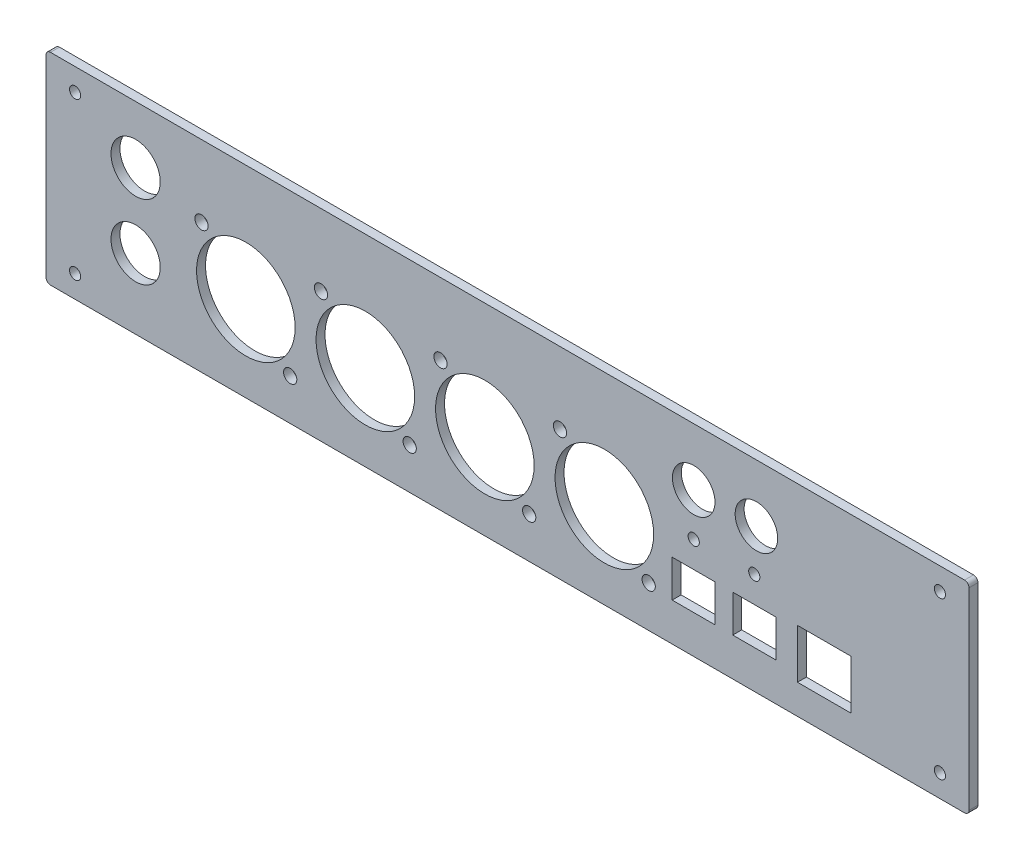
SolidWorks part; units mm, degrees
ref_plane "Front" through (0, 0, 0) normal (0, 0, 1) x (1, 0, 0)
ref_plane "Top" through (0, 0, 0) normal (0, 1, 0) x (1, 0, 0)
ref_plane "Right" through (0, 0, 0) normal (1, 0, 0) x (0, 0, -1)
sketch "草图5" plane through (0, 0, 0) normal (0, 0, 1) x (1, 0, 0)
  line L1 (-106.8845, -4.911) -> (99.1155, -4.911)
  line L2 (-106.8845, -4.911) -> (-106.8845, 40.089)
  line L3 (-106.8845, 40.089) -> (99.1155, 40.089)
  line L4 (99.1155, -4.911) -> (99.1155, 40.089)
  line L7 (-44.3845, -4.911) -> (40.6155, -4.911)
  line L9 (-44.3845, 40.089) -> (40.6155, 40.089)
  dimension "D1" = 206
  dimension "D2" = 45
  dimension "D3" = 85
extrude "凸台-拉伸3" add sketch "草图5" along normal blind 2 contours L4 L3 L2 L1
sketch "草图6" plane through (0, 0, 2) normal (0, 0, 1) x (1, 0, 0)
  line L0 (99.1155, -2.911) -> (-106.8845, -2.911) construction
  line L1 (99.1155, -4.911) -> (99.1155, 40.089) construction
  line L2 (-106.8845, -4.911) -> (-106.8845, 40.089) construction
  line L3 (-106.8845, -4.911) -> (99.1155, -4.911) construction
  line L4 (-106.8845, 0.089) -> (99.1155, 0.089) construction
  line L5 (99.1155, 1.689) -> (-106.8845, 1.689) construction
  line L6 (-1.8845, -2.911) -> (-1.8845, 40.089) construction
  line L7 (-81.8845, 14.189) -> (13.7097, 14.189) construction
  line L8 (-81.8845, 1.689) -> (109.1155, 1.689)
  line L9 (-81.8845, 1.689) -> (-81.8845, 0.089)
  line L10 (-81.8845, 0.089) -> (109.1155, 0.089)
  line L11 (109.1155, 1.689) -> (109.1155, 0.089)
  line L12 (61.4188, 10.089) -> (97.4452, 10.089)
  line L13 (-86.8845, 10.7454) -> (-86.8845, 27.2669) construction
  line L14 (-68.7606, 20.6651) -> (-44.2612, -3.8343) construction
  line L15 (-50.4178, 28.9923) -> (-20.8112, -0.6143) construction
  line L16 (-22.3851, 27.6296) -> (4.496, 0.7485) construction
  line L17 (17.7255, 14.189) -> (29.6473, 2.2672) construction
  line L18 (32.8655, 3.589) -> (42.4655, 3.589)
  line L19 (32.8655, 3.589) -> (32.8655, 11.889)
  line L20 (32.8655, 11.889) -> (42.4655, 11.889)
  line L21 (42.4655, 3.589) -> (42.4655, 11.889)
  line L22 (32.8655, 3.589) -> (42.4655, 11.889) construction
  line L23 (32.8655, 11.889) -> (42.4655, 3.589) construction
  line L24 (46.3855, 3.589) -> (55.9855, 3.589)
  line L25 (46.3855, 3.589) -> (46.3855, 11.889)
  line L26 (46.3855, 11.889) -> (55.9855, 11.889)
  line L27 (55.9855, 3.589) -> (55.9855, 11.889)
  line L28 (46.3855, 3.589) -> (55.9855, 11.889) construction
  line L29 (46.3855, 11.889) -> (55.9855, 3.589) construction
  line L30 (60.8255, 1.689) -> (72.8255, 1.689)
  line L31 (60.8255, 1.689) -> (60.8255, 12.689)
  line L32 (60.8255, 12.689) -> (72.8255, 12.689)
  line L33 (72.8255, 1.689) -> (72.8255, 12.689)
  line L34 (60.8255, 1.689) -> (72.8255, 12.689) construction
  line L35 (60.8255, 12.689) -> (72.8255, 1.689) construction
  circle A0 centre (-62.2845, 14.189) radius 11
  circle A1 centre (-35.6145, 14.189) radius 11
  circle A2 centre (-8.9445, 14.189) radius 11
  circle A3 centre (17.7255, 14.189) radius 11
  circle A4 centre (-72.1845, 24.089) radius 1.4749
  circle A5 centre (-52.3845, 4.289) radius 1.4749
  circle A6 centre (-45.5145, 24.089) radius 1.4749
  circle A7 centre (-25.7145, 4.289) radius 1.4749
  circle A8 centre (-18.8445, 24.089) radius 1.4749
  circle A9 centre (0.9555, 4.289) radius 1.4749
  circle A10 centre (7.8255, 24.089) radius 1.4749
  circle A11 centre (27.6255, 4.289) radius 1.4749
  circle A12 centre (37.6655, 17.739) radius 1.25
  circle A13 centre (51.1855, 17.739) radius 1.25
  circle A14 centre (51.6655, 27.2669) radius 4.75
  circle A15 centre (37.6655, 27.2669) radius 4.75
  circle A16 centre (-86.8845, 27.2669) radius 5.5
  circle A17 centre (-86.8845, 10.7454) radius 5.5
  circle A18 centre (-86.8845, 10.7454) radius 8 construction
  circle A19 centre (-86.8845, 27.2669) radius 8 construction
  text T0 "铜柱支撑高度" font "Century Gothic" height in points 9
  text T1 "pcb基板高度" font "Century Gothic" height in points 7
  point P31 (-81.8845, 0.889)
  point P35 (51.1855, 7.739)
  point P36 (37.6655, 7.739)
  point P37 (-35.6145, 14.189)
  point P42 (-62.2845, 14.189)
  point P43 (-8.9445, 14.189)
  point P73 (66.8255, 7.189)
  dimension "D6" = 22
  dimension "D7" = 22
  dimension "D8" = 22
  dimension "D9" = 22
  dimension "D33" = 2.5
  dimension "D34" = 2.5
  dimension "D40" = 9.5
  dimension "D41" = 9.5
  dimension "D43" = 11
  dimension "D44" = 11
  dimension "D46" = 16
  dimension "D48" = 16
  dimension "D1" = 2
  dimension "D2" = 3
  dimension "D3" = 1.6
  dimension "D4" = 191
  dimension "D5" = 12.5
  dimension "D10" = 9.9
  dimension "D11" = 9.9
  dimension "D12" = 45
  dimension "D13" = 45
  dimension "D14" = 45
  dimension "D15" = 45
  dimension "D16" = 9.9
  dimension "D17" = 9.9
  dimension "D18" = 9.9
  dimension "D19" = 9.9
  dimension "D20" = 9.9
  dimension "D21" = 9.9
  dimension "D22" = 19.6
  dimension "D23" = 26.67
  dimension "D24" = 26.67
  dimension "D25" = 26.67
  dimension "D26" = 9.6
  dimension "D27" = 9.6
  dimension "D28" = 8.3
  dimension "D29" = 8.3
  dimension "D30" = 13.52
  dimension "D31" = 1.9
  dimension "D32" = 5.24
  dimension "D35" = 10
  dimension "D36" = 10
  dimension "D37" = 4.84
  dimension "D38" = 11
  dimension "D39" = 12
  dimension "D42" = 25
  dimension "D45" = 14
  dimension "D47" = 8.4
  dimension "D49" = 5
extrude "切除-拉伸1" cut sketch "草图6" against normal blind 10 contours A1 | A2 | A3 | L18 L21 L20 L19 | L8 L33 L32 L31 | A13 | A12 | A11 | A10 | A8 | A7 | A9 | A6 | A5 | A4 | A15 | A0 | L27 L26 L25 L24 | A14 | A16 | A17 region at (66.8255, 7.189, 2) region at (37.6655, 7.739, 2) region at (-35.6145, 14.189, 2) region at (-8.9445, 14.189, 2) region at (17.7255, 14.189, 2) region at (-72.1845, 24.089, 2) region at (-52.3845, 4.289, 2) region at (-45.5145, 24.089, 2) region at (-25.7145, 4.289, 2) region at (-18.8445, 24.089, 2) region at (0.9555, 4.289, 2) region at (7.8255, 24.089, 2) region at (27.6255, 4.289, 2) region at (37.6655, 17.739, 2) region at (51.1855, 17.739, 2) region at (37.6655, 27.2669, 2)
sketch "草图1" plane through (0, 0, 0) normal (0, 0, 1) x (1, 0, 0)
  line L0 (92.6155, 0.089) -> (-100.3845, 0.089)
  line L1 (92.6155, 0.089) -> (92.6155, 35.089)
  line L2 (92.6155, 35.089) -> (-100.3845, 35.089)
  line L3 (-100.3845, 0.089) -> (-100.3845, 35.089)
  line L4 (92.6155, 0.089) -> (-100.3845, 35.089) construction
  line L5 (92.6155, 35.089) -> (-100.3845, 0.089) construction
  line L6 (-96.8845, 35.089) -> (-96.8845, 0.089) construction
  line L7 (-96.8675, 22.9489) -> (-96.8675, -12.0511) construction
  line L8 (89.1155, 23.1111) -> (89.1155, -11.8889) construction
  line L9 (-106.8845, 40.089) -> (99.1155, 40.089) construction
  circle A0 centre (-100.3845, 35.089) radius 1.25
  circle A1 centre (-100.3845, 35.089) radius 2.5
  circle A2 centre (-100.3845, 0.089) radius 1.25
  circle A3 centre (-100.3845, 0.089) radius 2.5
  circle A4 centre (92.6155, 0.089) radius 1.25
  circle A5 centre (92.6155, 0.089) radius 2.5
  circle A6 centre (92.6155, 35.089) radius 1.25
  circle A7 centre (92.6155, 35.089) radius 2.5
  point P0 (-3.8845, 17.589)
  point P13 (-3.8845, 17.589)
  point P24 (-3.8845, 40.089)
  dimension "D2" = 2.5
  dimension "D3" = 5
  dimension "D1" = 3.5
  dimension "D4" = 193
  dimension "D6" = 0.089
  dimension "D7" = 17.589
  dimension "D8" = 3.5
extrude "切除-拉伸7" cut sketch "草图1" along normal blind 70 contours A6 | A4 | A2 | A0
fillet "圆角1" radius 1 4 edges at (-106.8845, -4.911, 1) (-106.8845, 40.089, 1) (99.1155, -4.911, 1) (99.1155, 40.089, 1)
